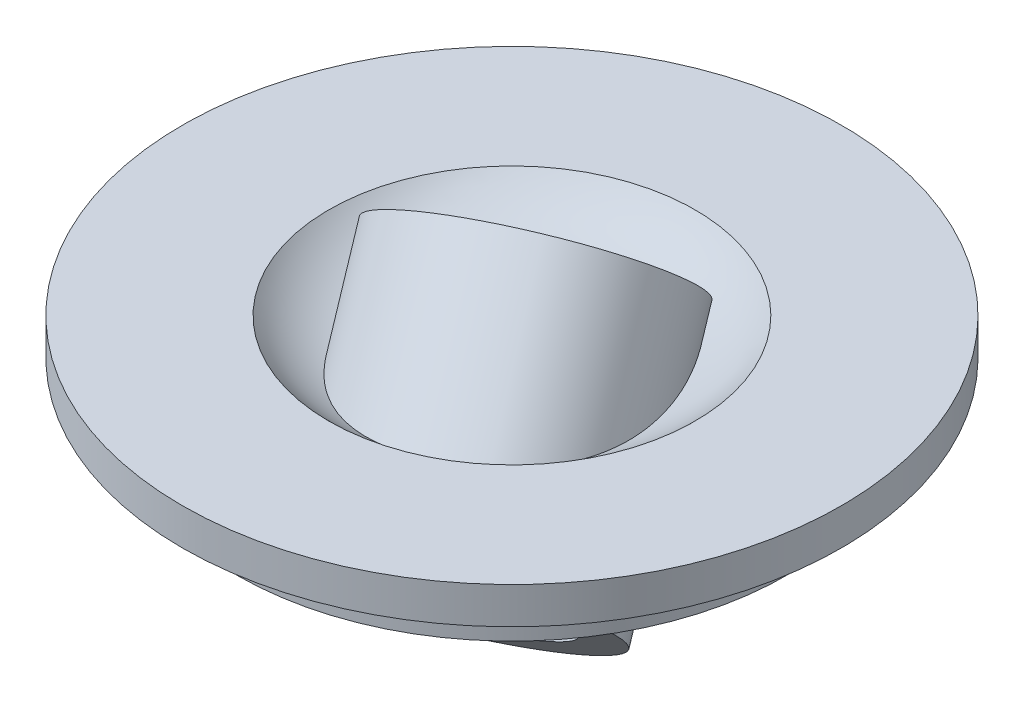
SolidWorks part; units mm, degrees
ref_plane "Front Plane" through (0, 0, 0) normal (0, 0, 1) x (1, 0, 0)
ref_plane "Top Plane" through (0, 0, 0) normal (0, 1, 0) x (1, 0, 0)
ref_plane "Right Plane" through (0, 0, 0) normal (1, 0, 0) x (0, 0, -1)
sketch "Sketch1" plane through (0, 2.1, 0) normal (0, 1, 0) x (1, 0, 0)
  circle A3 centre (-40.5, -30.5) radius 7.5 construction
  circle A4 centre (-40.5, -30.5) radius 7.5
  dimension "D1" = 15
extrude "Boss-Extrude2" add sketch "Sketch1" against normal up to surface (1.4 mm away)
sketch "Sketch3" plane through (0, 2.1, 0) normal (0, 1, 0) x (1, 0, 0)
  circle A0 centre (-40.5, -30.5) radius 5
  circle A1 centre (-40.5, -30.5) radius 9
  point P5 (-40.5, -30.5)
  dimension "D1" = 10
  dimension "D2" = 18
extrude "Boss-Extrude3" add sketch "Sketch3" along normal blind 1
fillet "Fillet1" radius 3 1 edges at (-40.5, 2.1, 35.5)
sketch3d "3DSketch1"
  line L3 (-38.9452, -1.4355, 33.6753) -> (-40.5, 2.1, 30.5)
  point P1 (-40.5, 2.1, 30.5)
  point P3 (-40.5, 2.1, 30.5)
  dimension "D2" = 5
ref_plane "Plane1" through (-38.9452, -1.4355, 33.6753) normal (-0.311, 0.7071, -0.6351) x (0.9504, 0.2314, -0.2078)
sketch "Sketch4" plane through (-38.9452, -1.4355, 33.6753) normal (-0.311, 0.7071, -0.6351) x (0.9504, 0.2314, -0.2078)
  circle A0 centre (0, 0) radius 2.5
  circle A1 centre (0, 0) radius 3.5
  dimension "D1" = 5
  dimension "D2" = 7
extrude "Boss-Extrude5" add sketch "Sketch4" along normal blind 7
sketch "Sketch5" plane through (3.2, -7.2765, 6.5351) normal (0.311, -0.7071, 0.6351) x (0.9504, 0.2314, -0.2078)
  circle A0 centre (-44.3436, 24.0949) radius 2.5 construction
  circle A1 centre (-44.3436, 24.0949) radius 2.5
extrude "Cut-Extrude1" cut sketch "Sketch5" against normal through all
